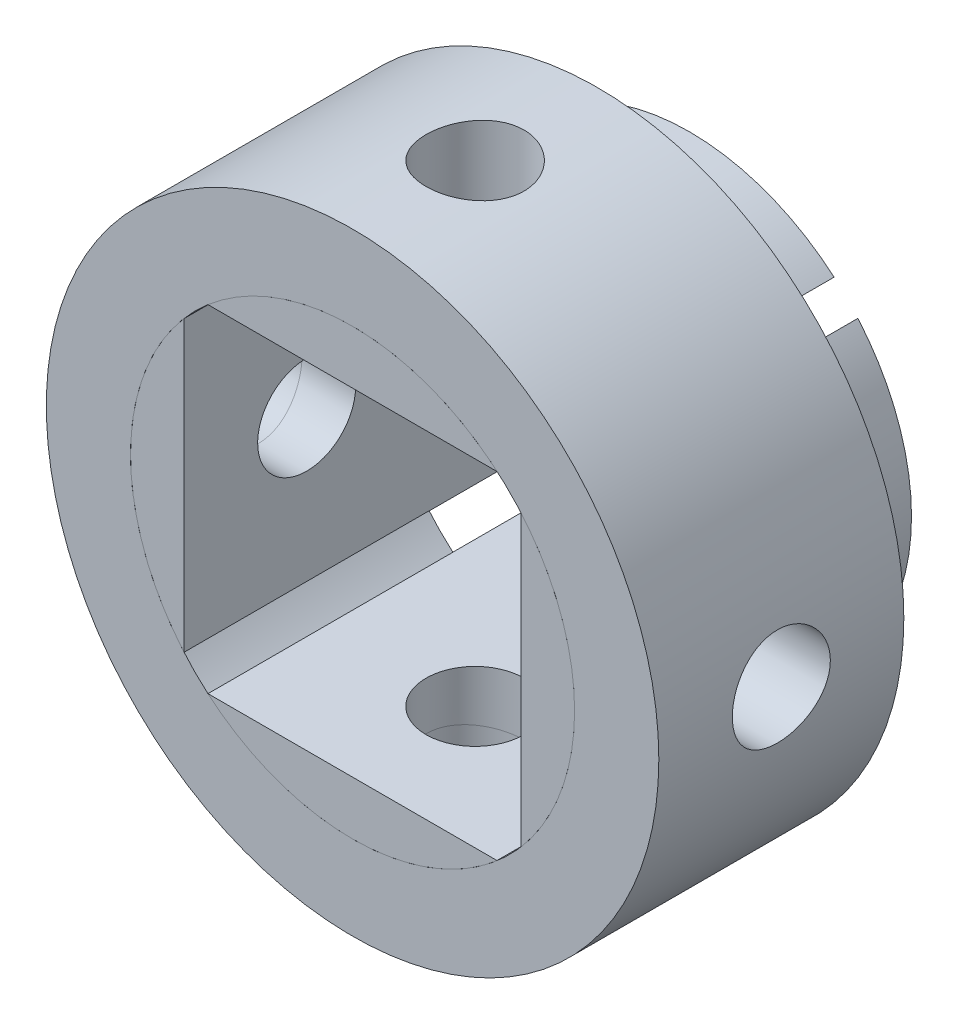
SolidWorks part; units mm, degrees
ref_plane "前视基准面" through (0, 0, 0) normal (0, 0, 1) x (1, 0, 0)
ref_plane "上视基准面" through (0, 0, 0) normal (0, 1, 0) x (1, 0, 0)
ref_plane "右视基准面" through (0, 0, 0) normal (1, 0, 0) x (0, 0, -1)
sketch "草图1" plane through (0, 0, 0) normal (0, 0, 1) x (1, 0, 0)
  circle A0 centre (0, 0) radius 7.25
  circle A1 centre (0, 0) radius 10
  dimension "D1" = 14.5
  dimension "D2" = 20
extrude "凸台-拉伸1" add sketch "草图1" along normal blind 8
sketch "草图2" plane through (0, 0, 0) normal (0, 1, 0) x (1, 0, 0)
  circle A0 centre (0, -4) radius 1.6
  dimension "D1" = 3.2
  dimension "D2" = 4
extrude "切除-拉伸1" cut sketch "草图2" against normal through all
sketch "草图3" plane through (0, 0, 0) normal (1, 0, 0) x (0, 0, -1)
  line L0 (-8, 10) -> (-8, -10) construction
  circle A0 centre (-4, 0) radius 1.6
  dimension "D1" = 3.2
  dimension "D2" = 4
extrude "切除-拉伸2" cut sketch "草图3" against normal through all
sketch "草图5" plane through (0, 0, 0) normal (0, 0, 1) x (1, 0, 0)
  line L0 (4.7236, 5.5) -> (-4.7236, 5.5)
  line L5 (-5.5, 5.5) -> (5.5, 5.5) construction
  line L6 (-5.5, 5.5) -> (-5.5, -5.5) construction
  line L7 (-5.5, -5.5) -> (5.5, -5.5) construction
  line L8 (5.5, 5.5) -> (5.5, -5.5) construction
  line L9 (-5.5, 5.5) -> (5.5, -5.5) construction
  line L10 (-5.5, -5.5) -> (5.5, 5.5) construction
  line L15 (5, 5) -> (-5, -5) construction
  line L16 (5, -5) -> (-5, 5) construction
  line L17 (5.5, -4.7236) -> (5.5, 4.7236)
  line L18 (-4.7236, -5.5) -> (4.7236, -5.5)
  line L19 (-5.5, 4.7236) -> (-5.5, -4.7236)
  arc A0 (4.7236, 5.5) -> (-4.7236, 5.5) centre (0, 0) ccw
  circle A1 centre (0, 0) radius 7.25 construction
  arc A2 (5.5, -4.7236) -> (5.5, 4.7236) centre (0, 0) ccw
  arc A3 (-4.7236, -5.5) -> (4.7236, -5.5) centre (0, 0) ccw
  arc A4 (-5.5, 4.7236) -> (-5.5, -4.7236) centre (0, 0) ccw
  point P0 (0, 0)
  point P4 (0, 0)
  point P25 (0, 0)
  dimension "D5" = 4
  dimension "D1" = 11
  dimension "D2" = 11
  dimension "D3" = 10
  dimension "D4" = 10
extrude "凸台-拉伸2" add sketch "草图5" against normal blind 3 and the other way blind 8 separate body
extrude "切除-拉伸3" cut sketch "草图2<2>" against normal through all
sketch "草图2<2>" plane through (0, 0, 0) normal (0, 1, 0) x (1, 0, 0) same geometry as "草图2"
extrude "切除-拉伸5" cut sketch "草图3<3>" against normal through all and the other way through all
sketch "草图3<3>" plane through (0, 0, 0) normal (1, 0, 0) x (0, 0, -1) same geometry as "草图3"
extrude "切除-拉伸6" cut sketch "草图2<3>" along normal through all
sketch "草图2<3>" plane through (0, 0, 0) normal (0, 1, 0) x (1, 0, 0) same geometry as "草图2"
